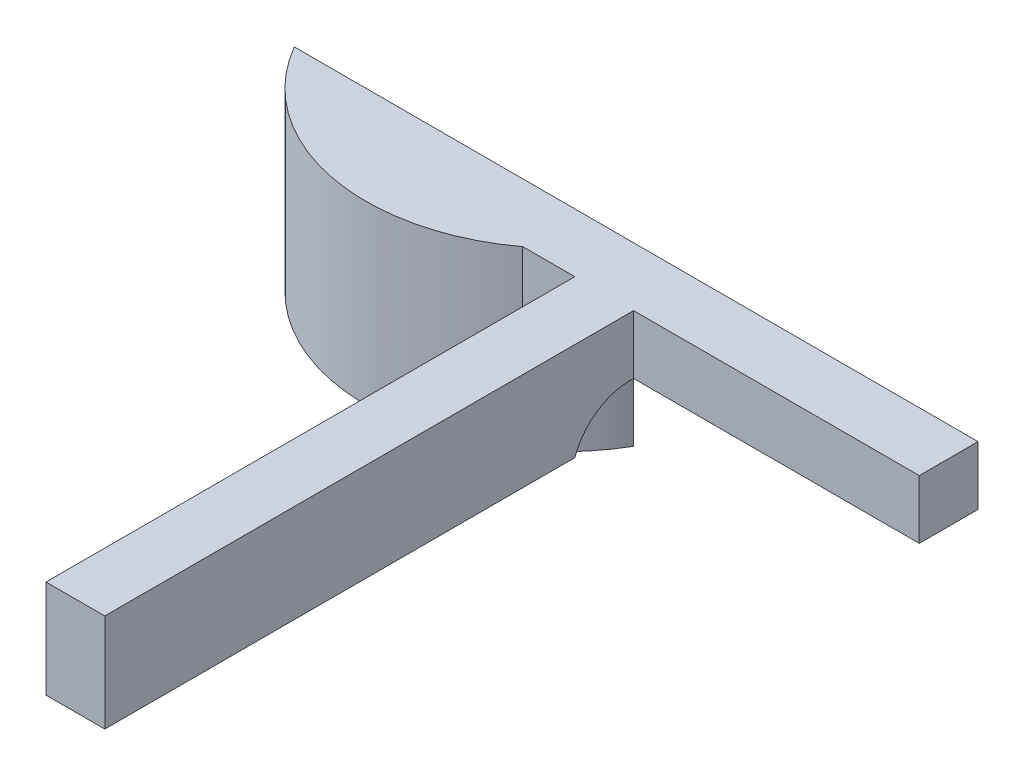
SolidWorks part; units mm, degrees
ref_plane "前视基准面" through (0, 0, 0) normal (0, 0, 1) x (1, 0, 0)
ref_plane "上视基准面" through (0, 0, 0) normal (0, 1, 0) x (1, 0, 0)
ref_plane "右视基准面" through (0, 0, 0) normal (1, 0, 0) x (0, 0, -1)
sketch "草图1" plane through (0, 0, 0) normal (0, 1, 0) x (1, 0, 0)
  line L0 (0, -8) -> (0, -5)
  line L1 (0, -5) -> (6.245, -5)
  line L2 (0, -5) -> (-6.245, -5)
  line L3 (6.245, -5) -> (26.245, -5)
  line L4 (0, -8) -> (26.245, -8)
  line L5 (26.245, -8) -> (26.245, -5)
  line L6 (-6.245, -5) -> (-8.6603, -5)
  line L7 (0, -10) -> (26.245, -10)
  line L8 (26.245, -10) -> (26.245, -8.1666)
  arc A0 (-6.245, -5) -> (6.245, -5) centre (0, 0) ccw
  arc A1 (-8.6603, -5) -> (8.6603, -5) centre (0, 0) ccw
extrude "凸台-拉伸1" add sketch "草图1" along normal blind 3 contours L2 A0 L0 | A0 L4 L5 L3 | A1 L4 A0 L6 | L4 A1 L3 A0 | L0 A0 L1 region at (-2.414, 0, 6.2217) region at (5.693, 0, 6.6757) region at (-2.0901, 0, 8.0247) region at (2.414, 0, 6.2217) region at (16.8627, 0, 6.535)
sketch "草图2" plane through (0, 0, 0) normal (0, -1, 0) x (1, 0, 0)
  line L0 (-8.6603, 5) -> (8.7924, 5)
  line L1 (-8.6603, 5) -> (26.245, 5) construction
  circle A0 centre (0, 0) radius 10
  circle A1 centre (0, 0) radius 8
  line M2 (-8.6603, 5) -> (26.245, 5)
  arc M5 (6, 8) -> (-8.6603, 5) centre (0, 0) ccw
extrude "凸台-拉伸2" add sketch "草图2" along normal blind 6 contours A1 A0 M2 M5 region at (-1.9687, 0, 9.6204)
sketch "草图3" plane through (0, 0, 5) normal (0, 0, -1) x (-1, 0, 0)
  line L0 (-8.6603, 3) -> (-11.6603, 3)
  line L1 (8.6603, 3) -> (-26.245, 3) construction
  line L2 (-11.6603, 3) -> (-11.6603, -2)
  line L3 (-11.6603, -2) -> (-8.6603, -2)
  line L4 (-8.6603, -6) -> (-8.6603, 0) construction
  line L5 (-8.6603, -2) -> (-8.6603, 3)
  line M9 (8.6603, 3) -> (-26.245, 3)
  line M11 (-26.245, 0) -> (-8.6603, 0)
extrude "凸台-拉伸6" add sketch "草图3" against normal blind 30 contours L5 L2 M11 M9 region at (10.1603, 1.5, 5)
fillet "圆角1" radius 1 1 edges at (7.482, 0, 6.6347)
sketch "草图5" plane through (0, 0, 35) normal (0, 0, 1) x (1, 0, 0)
  line L0 (8.6603, -2.0027) -> (8.6603, 0)
  line L2 (8.6603, -2.0027) -> (11.6603, -2.0027)
  line L3 (11.6603, -2.0027) -> (11.6603, 0)
  line L5 (8.6603, 0) -> (11.6603, 0)
extrude "凸台-拉伸9" add sketch "草图5" against normal blind 24
fillet "圆角2" radius 3 1 edges at (10.1603, 0, 11)
